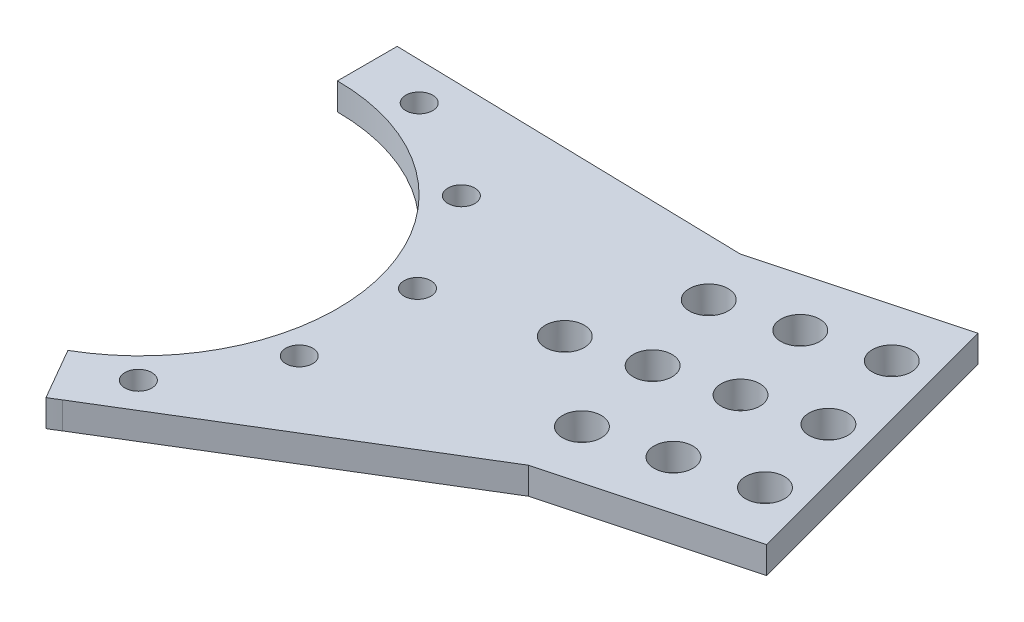
SolidWorks part; units mm, degrees
ref_plane "Front Plane" through (0, 0, 0) normal (0, 0, 1) x (1, 0, 0)
ref_plane "Top Plane" through (0, 0, 0) normal (0, 1, 0) x (1, 0, 0)
ref_plane "Right Plane" through (0, 0, 0) normal (1, 0, 0) x (0, 0, -1)
sketch "Sketch1" plane through (0, 0, 0) normal (0, 1, 0) x (1, 0, 0)
  line L0 (0, 33) -> (0, 43)
  line L1 (16.5, -28.5788) -> (21.5, -37.2391)
  arc A0 (0, 43) -> (21.5, -37.2391) centre (0, 0) cw
  arc A1 (0, 33) -> (16.5, -28.5788) centre (0, 0) cw
  dimension "D1" = 150
  dimension "D2" = 33
  dimension "D3" = 43
extrude "Boss-Extrude1" add sketch "Sketch1" along normal mid plane 4.5
sketch "Sketch4" plane through (0, 0, 0) normal (0, 1, 0) x (1, 0, 0)
  line L0 (0, 0) -> (64.2341, 17.2115) construction
  line L1 (90.1221, 50.0301) -> (25.4051, 32.6892)
  line L2 (90.1221, 50.0301) -> (103.0631, 1.7338)
  line L3 (25.4051, 32.6892) -> (38.346, -15.6071)
  line L4 (103.0631, 1.7338) -> (38.346, -15.6071)
  line L5 (31.8756, 8.541) -> (96.5926, 25.8819) construction
  line L6 (57.7636, 41.3596) -> (70.7045, -6.9367) construction
  line L7 (0, 43) -> (0, 33) construction
  arc A1 (16.5, -28.5788) -> (0, 33) centre (0, 0) ccw construction
  dimension "D1" = 75
  dimension "D2" = 100
  dimension "D3" = 50
extrude "Boss-Extrude2" add sketch "Sketch4" along normal mid plane 4.5
sketch "Sketch5" plane through (0, 0, 0) normal (0, 1, 0) x (1, 0, 0)
  line L0 (0, 0) -> (96.5926, 25.8819) construction
  line L1 (103.0631, 1.7338) -> (90.1221, 50.0301) construction
  line L2 (0, 43) -> (58.7226, 41.6166)
  line L3 (90.1221, 50.0301) -> (27.3231, 33.2031) construction
  line L4 (58.7226, 41.6166) -> (27.3231, 33.2031)
  line L5 (27.3231, 33.2031) -> (0, 43)
  line L6 (71.6636, -6.6797) -> (40.2641, -15.0932)
  line L7 (21.5, -37.2391) -> (71.6636, -6.6797)
  line L8 (40.2641, -15.0932) -> (21.5, -37.2391)
extrude "Boss-Extrude3" add sketch "Sketch5" along normal mid plane 4.5
sketch "Sketch2" plane through (0, 2.25, 0) normal (0, 1, 0) x (1, 0, 0)
  arc A0 (18.6469, -33.1103) -> (0, 38) centre (0, 0) ccw construction
  circle A1 centre (36.7573, 9.6387) radius 2.25
  dimension "D1" = 4.5
  dimension "D2" = 38
extrude "Cut-Extrude1" cut sketch "Sketch2" against normal through all both and the other way through all
pattern_circular "CirPattern1" count 3 every 30 about axis through (0, 2.25, 0) along (0, -1, 0) of "Cut-Extrude1" other way count 3
sketch "Sketch6" plane through (0, 2.25, 0) normal (0, 1, 0) x (1, 0, 0)
  line L0 (0, 0) -> (96.5926, 25.8819) construction
  line L1 (103.0631, 1.7338) -> (90.1221, 50.0301) construction
  line L2 (86.9147, 38.8179) -> (94.6793, 9.8401) construction
  circle A0 centre (94.6793, 9.8401) radius 3.25
  circle A1 centre (86.9147, 38.8179) radius 3.25
  point P8 (90.797, 24.329)
  dimension "D1" = 6.5
  dimension "D2" = 30
  dimension "D3" = 6
extrude "Cut-Extrude2" cut sketch "Sketch6" against normal through all both and the other way through all
pattern_linear "LPattern1" count 3 spacing 12.5 along (-0.9659, 0, 0.2588) of "Cut-Extrude2"
sketch "Sketch7" plane through (0, 2.25, 0) normal (0, 1, 0) x (1, 0, 0)
  line L0 (0, 0) -> (96.5926, 25.8819) construction
  line L1 (103.0631, 1.7338) -> (90.1221, 50.0301) construction
  circle A0 centre (90.797, 24.329) radius 3.25
  dimension "D1" = 6.5
  dimension "D2" = 6
extrude "Cut-Extrude3" cut sketch "Sketch7" against normal blind 10
pattern_linear "LPattern2" count 4 spacing 12 along (-0.9659, 0, 0.2588) of "Cut-Extrude3"
sketch "Sketch8" plane through (0, 0, 0) normal (0, 1, 0) x (1, 0, 0)
  line L0 (0, 33) -> (0, 0)
  line L1 (0, 33) -> (5, 33)
  line L2 (0, 0) -> (5, 0)
  line L3 (5, 33) -> (5, 0)
  line L4 (16.5, -28.5788) -> (0, 0)
  line L5 (16.5, -28.5788) -> (20.8301, -26.0788)
  line L6 (0, 0) -> (4.3301, 2.5)
  line L7 (20.8301, -26.0788) -> (4.3301, 2.5)
  line L8 (0, 0) -> (36.7573, 9.6387) construction
  line L9 (32.91, 11.2143) -> (-0.6341, 2.4182)
  line L10 (32.91, 11.2143) -> (34.1782, 6.3778)
  line L11 (-0.6341, 2.4182) -> (0.6341, -2.4182)
  line L12 (34.1782, 6.3778) -> (0.6341, -2.4182)
  line L13 (0, 0) -> (33.5441, 8.7961) construction
  line L14 (16.1379, 6.8163) -> (17.4062, 1.9798) construction
  circle A0 centre (0, 0) radius 9
  circle A1 centre (0, 0) radius 15
  point P15 (16.772, 4.398)
  dimension "D1" = 18
  dimension "D2" = 30
  dimension "D3" = 5
extrude "Boss-Extrude4" [suppressed] add sketch "Sketch8" along normal mid plane 4.5 contours L0 A1 L4 A0 | L9 A1 L3 A0 | L7 A1 L12 A0 | A1 L4 L5 L7 | L4 A1 L7 A0 | A1 L3 L1 L0 | L3 A1 L0 A0 | L12 A1 L9 A0 | A1 L12 L10 L9
